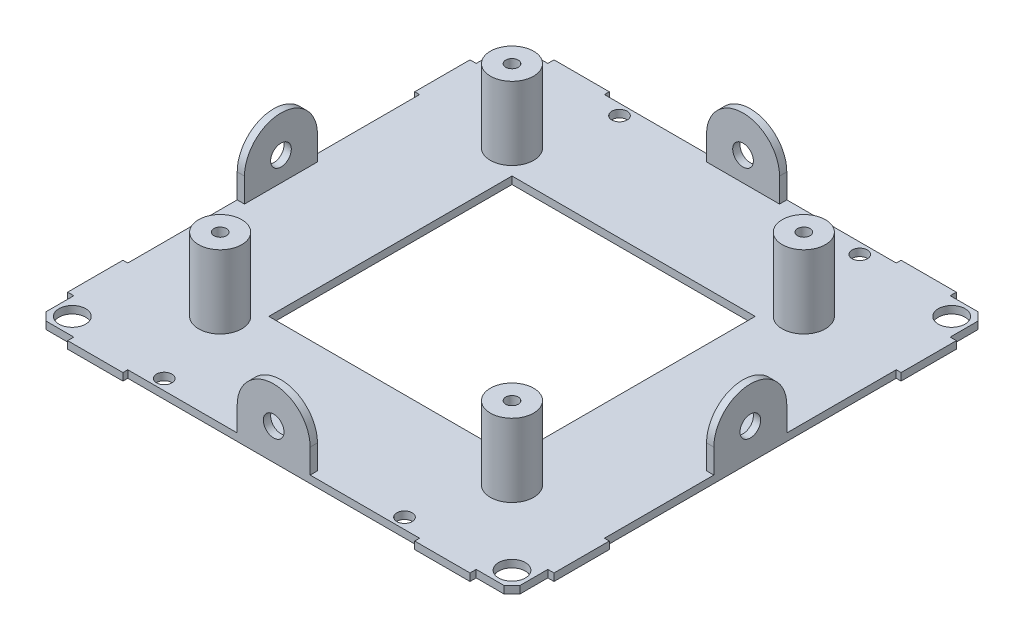
SolidWorks part; units mm, degrees
ref_plane "Front Plane" through (0, 0, 0) normal (0, 0, 1) x (1, 0, 0)
ref_plane "Top Plane" through (0, 0, 0) normal (0, 1, 0) x (1, 0, 0)
ref_plane "Right Plane" through (0, 0, 0) normal (1, 0, 0) x (0, 0, -1)
sketch "Sketch1" plane through (0, 0, 0) normal (0, 1, 0) x (1, 0, 0)
  line L0 (-50, 50) -> (-41.364, 50)
  line L1 (-50, -50) -> (50, -50)
  line L2 (-50, -50) -> (-50, 50)
  line L3 (-50, 50) -> (50, 50)
  line L4 (50, -50) -> (50, 50)
  line L5 (-50, -50) -> (50, 50) construction
  line L6 (-50, 50) -> (50, -50) construction
  line L7 (-50, 50) -> (-50, 41.364)
  line L8 (-50, 41.364) -> (-48.73, 41.364)
  line L9 (-48.73, 41.364) -> (-48.73, 47.079)
  line L10 (-41.364, 50) -> (-41.364, 48.73)
  line L11 (-41.364, 48.73) -> (-47.079, 48.73)
  line L12 (-47.079, 48.73) -> (-48.73, 47.079)
  line L13 (-50, 50) -> (-45.2, 50) construction
  line L14 (-45.2, 50) -> (-45.2, 45.2) construction
  line L15 (50, 50) -> (50, 41.364)
  line L16 (50, 41.364) -> (48.73, 41.364)
  line L17 (48.73, 41.364) -> (48.73, 47.079)
  line L18 (48.73, 47.079) -> (47.079, 48.73)
  line L19 (41.364, 48.73) -> (47.079, 48.73)
  line L20 (41.364, 50) -> (41.364, 48.73)
  line L21 (50, 50) -> (41.364, 50)
  line L22 (50, -50) -> (41.364, -50)
  line L23 (41.364, -50) -> (41.364, -48.73)
  line L24 (41.364, -48.73) -> (47.079, -48.73)
  line L25 (47.079, -48.73) -> (48.73, -47.079)
  line L26 (48.73, -41.364) -> (48.73, -47.079)
  line L27 (50, -41.364) -> (48.73, -41.364)
  line L28 (50, -50) -> (50, -41.364)
  line L29 (-50, -50) -> (-50, -41.364)
  line L30 (-50, -41.364) -> (-48.73, -41.364)
  line L31 (-48.73, -41.364) -> (-48.73, -47.079)
  line L32 (-48.73, -47.079) -> (-47.079, -48.73)
  line L33 (-41.364, -48.73) -> (-47.079, -48.73)
  line L34 (-41.364, -50) -> (-41.364, -48.73)
  line L35 (-50, -50) -> (-41.364, -50)
  line L36 (0, -50) -> (0, 50) construction
  line L37 (-1000, 46.8) -> (49000, 46.8) construction
  line L38 (24.7, 46.8) -> (-24.7, 46.8)
  line L39 (-1000, 0) -> (49000, 0) construction
  line L41 (-25, -25) -> (25, -25)
  line L42 (-25, -25) -> (-25, 25)
  line L43 (-25, 25) -> (25, 25)
  line L44 (25, -25) -> (25, 25)
  line L45 (-25, -25) -> (25, 25) construction
  line L46 (-25, 25) -> (25, -25) construction
  circle A0 centre (-45.2, 45.2) radius 2.7503
  circle A1 centre (45.2, 45.2) radius 2.7503
  circle A2 centre (45.2, -45.2) radius 2.7503
  circle A3 centre (-45.2, -45.2) radius 2.7503
  circle A4 centre (-24.7, 46.8) radius 1.575
  circle A5 centre (24.7, 46.8) radius 1.575
  circle A6 centre (24.7, -46.8) radius 1.575
  circle A7 centre (-24.7, -46.8) radius 1.575
  point P0 (0, 0)
  point P15 (0, 46.8)
  point P45 (0, 0)
  point P46 (0, 0)
  point P48 (-24.7, 46.8)
  point P53 (0, 46.8)
  point P61 (25, 25)
  point P63 (0, 0)
  dimension "D4" = 4
  dimension "D1" = 100
  dimension "D2" = 100
  dimension "D3" = 8.636
  dimension "D5" = 3.2
  dimension "D6" = 24.7
extrude "Boss-Extrude1" add sketch "Sketch1" along normal blind 1.524 contours L37 A5 L38 A4 A0 L9 L8 L2 L30 L31 L32 L33 L34 L1 L23 L24 L25 L26 L27 L4 L16 L17 A1 A2 A3 A6 A7 region at (0, 0, -48.5858)
sketch "Sketch2" plane through (0, 1.524, 0) normal (0, 1, 0) x (1, 0, 0)
  line L0 (0, -1000) -> (0, 49000) construction
  line L1 (0, 50) -> (0, 45) construction
  line L2 (-41.364, 50) -> (41.364, 50) construction
  line L3 (-7.5, 47.5) -> (7.5, 47.5) construction
  line L4 (-7.5, 47.5) -> (7.5, 47.5)
  line L5 (-7.5, 47.5) -> (-7.5, 50)
  line L6 (7.5, 47.5) -> (7.5, 50)
  line L7 (-7.5, 50) -> (7.5, 50)
  line L8 (47.5, 7.5) -> (47.5, -7.5)
  line L9 (47.5, 7.5) -> (50, 7.5)
  line L10 (50, 7.5) -> (50, -7.5)
  line L11 (47.5, -7.5) -> (50, -7.5)
  line L12 (7.5, -47.5) -> (-7.5, -47.5)
  line L13 (7.5, -47.5) -> (7.5, -50)
  line L14 (7.5, -50) -> (-7.5, -50)
  line L15 (-7.5, -47.5) -> (-7.5, -50)
  line L16 (-47.5, -7.5) -> (-47.5, 7.5)
  line L17 (-47.5, -7.5) -> (-50, -7.5)
  line L18 (-50, -7.5) -> (-50, 7.5)
  line L19 (-47.5, 7.5) -> (-50, 7.5)
  point P10 (0, 47.5)
  point P27 (0, 0)
  dimension "D1" = 15
  dimension "D2" = 4
extrude "Boss-Extrude2" add sketch "Sketch2" along normal blind 12.476 contours L4 L5 L7 L6 | L8 L11 L10 L9 | L12 L15 L14 L13 | L16 L19 L18 L17
sketch "Sketch3" plane through (0, 0, 50) normal (0, 0, 1) x (1, 0, 0)
  line L0 (-1007.5, 1.524) -> (48992.5, 1.524) construction
  line L1 (7.5, 1.524) -> (-7.5, 1.524) construction
  line L2 (-7.5, 14) -> (-7.5, 1.524) construction
  line L3 (0, 1.524) -> (0, 6.5) construction
  line L4 (7.5, 14) -> (7.5, 1.524) construction
  line L5 (7.5, 6.5) -> (7.5, 14)
  line L6 (7.5, 14) -> (-7.5, 14)
  line L7 (-7.5, 14) -> (-7.5, 6.5)
  circle A0 centre (0, 6.5) radius 2.125
  arc A1 (-7.5, 6.5) -> (7.5, 6.5) centre (0, 6.5) cw
  line M4 (7.5, 1.524) -> (7.5, 14)
  line M5 (7.5, 14) -> (-7.5, 14)
  line M6 (-7.5, 14) -> (-7.5, 1.524)
extrude "Cut-Extrude1" cut sketch "Sketch3" against normal through all both and the other way through all contours A1 M5 M4 | A1 L6 M6 | A0 region at (5.8247, 12.3247, 50) region at (-5.8247, 12.3247, 50) region at (0, 6.5, 50)
sketch "Sketch4" plane through (-50, 0, 0) normal (-1, 0, 0) x (0, 0, 1)
  line L0 (-992.5, 1.524) -> (49007.5, 1.524) construction
  line L1 (-7.5, 1.524) -> (7.5, 1.524) construction
  line L2 (41.364, 1.524) -> (7.5, 1.524) construction
  line L3 (0, 1.524) -> (0, 6.5) construction
  line L4 (7.5, 14) -> (7.5, 1.524) construction
  line L5 (-7.5, 14) -> (-7.5, 1.524) construction
  line L6 (7.5, 6.5) -> (7.5, 14)
  line L7 (7.5, 14) -> (-7.5, 14)
  line L8 (-7.5, 14) -> (-7.5, 6.5)
  circle A0 centre (0, 6.5) radius 2.125
  arc A1 (7.5, 6.5) -> (-7.5, 6.5) centre (0, 6.5) ccw
  line M4 (7.5, 1.524) -> (7.5, 14)
  line M5 (7.5, 14) -> (-7.5, 14)
  line M6 (-7.5, 14) -> (-7.5, 1.524)
extrude "Cut-Extrude2" cut sketch "Sketch4" against normal through all both and the other way through all contours A0 | A1 M4 M5 | A1 L7 M6 region at (-50, 12.3247, 5.8247) region at (-50, 12.3247, -5.8247) region at (-50, 6.5, 0)
sketch "Sketch5" plane through (0, 0, 0) normal (0, -1, 0) x (1, 0, 0)
  line L0 (-1000, -50) -> (49000, -50) construction
  line L1 (-7.5, -50) -> (7.5, -50) construction
  line L2 (0, -1000) -> (0, 49000) construction
  line L3 (-30, -50) -> (30, -50) construction
  line L4 (-30, -50) -> (-30, -49) construction
  line L5 (-50, 30) -> (-49, 30) construction
  line L6 (-30, -49) -> (30, -49)
  line L7 (-30, -49) -> (-30, -50)
  line L8 (-30, -50) -> (30, -50)
  line L9 (30, -49) -> (30, -50)
  line L10 (-49, 30) -> (-50, 30)
  line L11 (-49, 30) -> (-49, -30)
  line L12 (-49, -30) -> (-50, -30)
  line L13 (-50, 30) -> (-50, -30)
  line L14 (30, 50) -> (30, 49) construction
  line L15 (30, 49) -> (30, 50)
  line L16 (30, 49) -> (-30, 49)
  line L17 (-30, 49) -> (-30, 50)
  line L18 (30, 50) -> (-30, 50)
  line L19 (50, -30) -> (49, -30) construction
  line L20 (49, -30) -> (50, -30)
  line L21 (49, -30) -> (49, 30)
  line L22 (49, 30) -> (50, 30)
  line L23 (50, -30) -> (50, 30)
  point P5 (0, -50)
  point P11 (0, -50)
  point P28 (0, 0)
  dimension "D1" = 4
extrude "Cut-Extrude3" cut sketch "Sketch5" against normal through all both and the other way through all
sketch "Sketch6" plane through (0, 1.524, 0) normal (0, 1, 0) x (1, 0, 0)
  circle A0 centre (30, 30) radius 4.445
  circle A1 centre (30, -30) radius 4.445
  circle A2 centre (-30, -30) radius 4.445
  circle A3 centre (-30, 30) radius 4.445
  point P0 (30, 30)
  point P12 (0, 0)
  dimension "D1" = 4
extrude "Boss-Extrude3" add sketch "Sketch6" along normal blind 15
hole_wizard "#5-40 Tapped Hole1" positions "Sketch7" profile "Sketch8" tap size "#5-40" standard "ANSI Inch"
sketch "Sketch7" plane through (0, 16.524, 0) normal (0, 1, 0) x (1, 0, 0)
  point P0 (-17.223, 16.8349)
  point P2 (-17.223, 16.8349)
  point P5 (-30, 30)
  point P8 (-30, -30)
  point P11 (30, -30)
  point P14 (30, 30)
sketch "Sketch8" plane through (-17.223, 16.524, -16.8349) normal (1, 0, 0) x (0, 0, 1)
  line L0 (0, 0) -> (0, 15.7745)
  line L1 (0, 15.7745) -> (1.289, 15)
  line L2 (1.289, 15) -> (1.289, 0)
  line L5 (1.289, 0) -> (0, 0)
  line L10 (0, 15.7745) -> (-1.2891, 15) construction
  line L11 (0, -6.35) -> (0, 107.95) construction
  dimension "Tap Drill Dia." = 2.5781
  dimension "Tap Drill Depth" = 15
  dimension "Drill Angle" = 118
cosmetic thread "Hole Thread1" parameters "D1"=15, "D2"=3.175
cosmetic thread "Hole Thread2" parameters "D1"=15, "D2"=3.175
cosmetic thread "Hole Thread3" parameters "D1"=15, "D2"=3.175
cosmetic thread "Hole Thread4" parameters "D1"=15, "D2"=3.175
